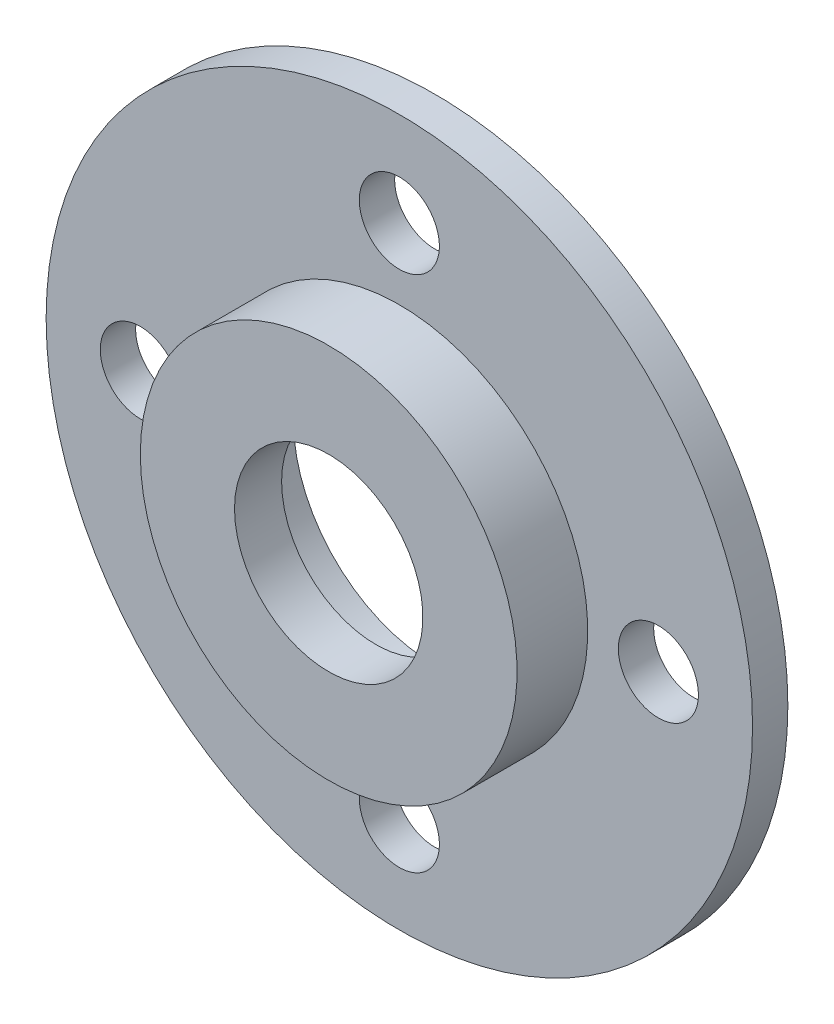
SolidWorks part; units mm, degrees
ref_plane "Front Plane" through (0, 0, 0) normal (0, 0, 1) x (1, 0, 0)
ref_plane "Top Plane" through (0, 0, 0) normal (0, 1, 0) x (1, 0, 0)
ref_plane "Right Plane" through (0, 0, 0) normal (1, 0, 0) x (0, 0, -1)
sketch "Sketch1" plane through (0, 0, 0) normal (0, 1, 0) x (1, 0, 0)
  line L8 (0, 9.6513) -> (0, -9.5751) construction
  line L9 (4, 1.6987) -> (4, -0.3013)
  line L17 (4, -0.3013) -> (8, -0.3013)
  line L21 (15, 4.1987) -> (6, 4.1987)
  line L22 (6, 4.1987) -> (6, 1.6987)
  line L23 (6, 1.6987) -> (4, 1.6987)
  line L24 (8, -0.3013) -> (8, 2.6987)
  line L25 (8, 2.6987) -> (15, 2.6987)
  line L26 (15, 2.6987) -> (15, 4.1987)
  dimension "D1" = 4
  dimension "D2" = 4
  dimension "D3" = 6
  dimension "D4" = 2.5
  dimension "D5" = 1.5
  dimension "D6" = 15
revolve "Revolve1" add sketch "Sketch1" angle 360 about L8
sketch "Sketch2" plane through (0, 0, -4.1987) normal (0, 0, -1) x (-1, 0, 0)
  point P0 (-11, 0)
  dimension "D1" = 11
hole_wizard "M3 Clearance Hole1" positions "Sketch3" profile "Sketch4" hole size "M3" standard "ISO" end condition through all
sketch "Sketch3" plane through (0, 0, -4.1987) normal (0, 0, -1) x (-1, 0, 0)
  point P0 (-11, 0)
sketch "Sketch4" plane through (11, 0, -4.1987) normal (1, 0, 0) x (0, 1, 0)
  line L0 (0, 0) -> (0, 4.5)
  line L1 (0, 4.5) -> (1.7, 4.5)
  line L2 (1.7, 4.5) -> (1.7, 0)
  line L5 (1.7, 0) -> (0, 0)
  line L11 (0, -6.35) -> (0, 107.95) construction
  dimension "Thru Hole Dia." = 3.4
  dimension "Thru Hole Depth" = 4.5
ref_axis "Axis1" through (0, 0, 11.6763) along (0, 0, -1)
pattern_circular "CirPattern1" count 4 every 90 about axis through (0, 0, 11.6763) along (0, 0, -1) of "M3 Clearance Hole1"
